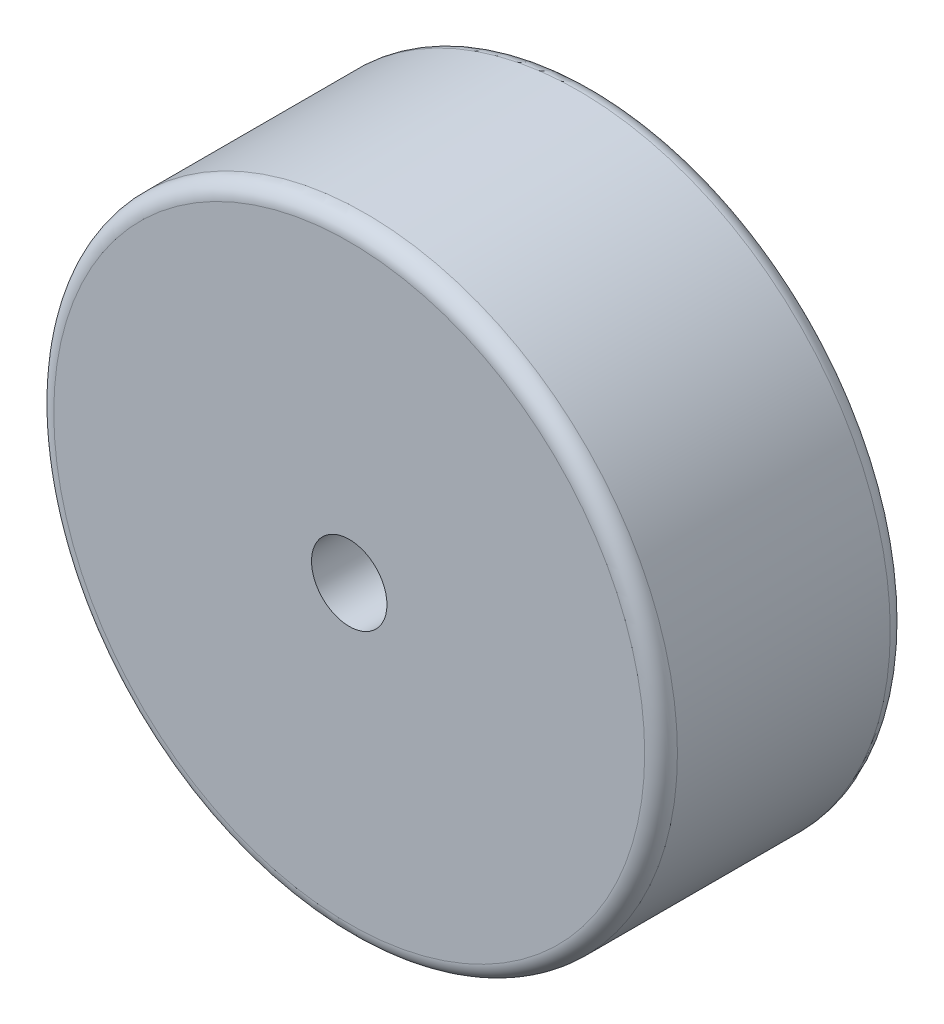
SolidWorks part; units mm, degrees
ref_plane "Front Plane" through (0, 0, 0) normal (0, 0, 1) x (1, 0, 0)
ref_plane "Top Plane" through (0, 0, 0) normal (0, 1, 0) x (1, 0, 0)
ref_plane "Right Plane" through (0, 0, 0) normal (1, 0, 0) x (0, 0, -1)
sketch "body sketch" plane through (0, 0, 0) normal (0, 0, 1) x (1, 0, 0)
  circle A0 centre (0, 0) radius 19.05
  dimension "D1" = 38.1
extrude "wheel body" add sketch "body sketch" along normal mid plane 15 contours A0
sketch "hole sketch" plane through (0, 0, 7.5) normal (0, 0, 1) x (1, 0, 0)
  circle A0 centre (0, 0) radius 2.305
  dimension "D1" = 4.61
fillet "fillet wheel" radius 1 2 edges at (19.05, 0, -7.5) (19.05, 0, 7.5)
extrude "hole shaft" cut sketch "hole sketch" against normal blind 15 contours A0
